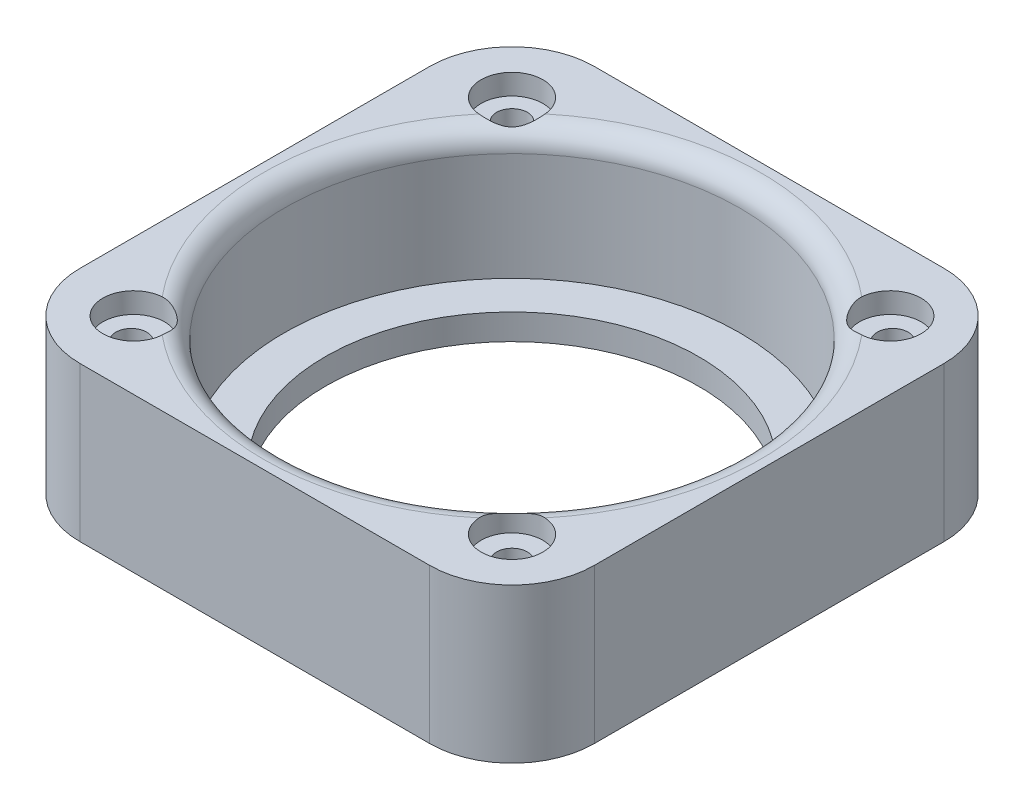
SolidWorks part; units mm, degrees
ref_plane "前视基准面" through (0, 0, 0) normal (0, 0, 1) x (1, 0, 0)
ref_plane "上视基准面" through (0, 0, 0) normal (0, 1, 0) x (1, 0, 0)
ref_plane "右视基准面" through (0, 0, 0) normal (1, 0, 0) x (0, 0, -1)
sketch "草图1" plane through (0, 0, 0) normal (0, 1, 0) x (1, 0, 0)
  circle A0 centre (0, 0) radius 25
extrude "凸台-拉伸1" add sketch "草图1" along normal blind 15
sketch "草图2" plane through (0, 15, 0) normal (0, 1, 0) x (1, 0, 0)
  circle A0 centre (0, 0) radius 22.15
  dimension "D1" = 44.3
extrude "切除-拉伸1" cut sketch "草图2" against normal blind 12.5
sketch "草图3" plane through (0, 2.5, 0) normal (0, 1, 0) x (1, 0, 0)
  circle A0 centre (0, 0) radius 18.15
  circle A1 centre (0, 0) radius 22.15 construction
  dimension "D1" = 4
extrude "切除-拉伸2" cut sketch "草图3" against normal blind 12.5
sketch "草图4" plane through (0, 0, 0) normal (0, 1, 0) x (1, 0, 0)
  line L1 (-25, 25) -> (25, 25)
  line L2 (-25, 25) -> (-25, -25)
  line L3 (-25, -25) -> (25, -25)
  line L4 (25, 25) -> (25, -25)
  line L5 (-25, 25) -> (25, -25) construction
  line L6 (-25, -25) -> (25, 25) construction
  circle A0 centre (0, 0) radius 25
  circle A1 centre (-18.3848, 18.3848) radius 1.5
  circle A2 centre (18.6152, 18.3848) radius 1.5
  circle A3 centre (18.6152, -18.6152) radius 1.5
  circle A4 centre (-18.3848, -18.6152) radius 1.5
  point P0 (0, 0)
  point P20 (0.1152, -0.1152)
  dimension "D3" = 3
  dimension "D4" = 26
  dimension "D6" = 37
  dimension "D7" = 37
  dimension "D1" = 50
  dimension "D2" = 50
  dimension "D5" = 4
extrude "凸台-拉伸2" add sketch "草图4" along normal blind 15 contours A0 L1 L2 | A0 L4 L1 | A0 L2 L3 | A0 L3 L4 region at (-19.4617, 0, -19.4617) region at (12.5, 0, -24.6464) region at (-23.5702, 0, 9.3406) region at (24.6464, 0, 12.5)
fillet "圆角1" radius 8 4 edges at (-25, 7.5, 25) (25, 7.5, 25) (25, 7.5, -25) (-25, 7.5, -25)
sketch "草图5" plane through (0, 15, 0) normal (0, 1, 0) x (1, 0, 0)
  circle A0 centre (-18.3848, 18.3848) radius 1.5
  circle A1 centre (18.6152, 18.3848) radius 1.5
  circle A2 centre (18.6152, -18.6152) radius 1.5
  circle A3 centre (-18.3848, -18.6152) radius 1.5
  point P12 (0.1152, -0.1152)
  dimension "D1" = 4
extrude "切除-拉伸3" cut sketch "草图5" against normal blind 15
sketch "草图6" plane through (0, 15, 0) normal (0, 1, 0) x (1, 0, 0)
  circle A0 centre (-18.3848, 18.3848) radius 3
  dimension "D1" = 6
extrude "切除-拉伸4" cut sketch "草图6" against normal blind 2
pattern_circular "阵列(圆周)1" count 4 over 360 about axis through (0, -10, 0) along (0, 1, 0) of "切除-拉伸4"
sketch "草图7" plane through (0, 0, 0) normal (0, -1, 0) x (1, 0, 0)
  line L0 (15.5416, 17.8176) -> (17.7692, 15.5546)
  line L1 (-15.3241, 17.7692) -> (-16.1217, 20.8428)
  line L2 (-16.1217, 20.8428) -> (-19.1824, 21.6888)
  line L3 (-19.1824, 21.6888) -> (-21.4454, 19.4613)
  line L4 (-21.4454, 19.4613) -> (-20.6478, 16.3877)
  line L5 (-20.6478, 16.3877) -> (-17.5872, 15.5416)
  line L6 (-17.5872, 15.5416) -> (-15.3241, 17.7692)
  line L7 (16.3877, 20.8783) -> (15.5416, 17.8176)
  line L8 (19.4613, 21.6759) -> (16.3877, 20.8783)
  line L9 (21.6888, 19.4128) -> (19.4613, 21.6759)
  line L10 (20.8428, 16.3522) -> (21.6888, 19.4128)
  line L11 (17.7692, 15.5546) -> (20.8428, 16.3522)
  line L12 (17.8176, -15.3112) -> (15.5546, -17.5387)
  line L13 (20.8783, -16.1572) -> (17.8176, -15.3112)
  line L14 (21.6759, -19.2308) -> (20.8783, -16.1572)
  line L15 (19.4128, -21.4584) -> (21.6759, -19.2308)
  line L16 (16.3522, -20.6123) -> (19.4128, -21.4584)
  line L17 (15.5546, -17.5387) -> (16.3522, -20.6123)
  line L18 (-15.3112, -17.5872) -> (-17.5387, -15.3241)
  line L19 (-16.1572, -20.6478) -> (-15.3112, -17.5872)
  line L20 (-19.2308, -21.4454) -> (-16.1572, -20.6478)
  line L21 (-21.4584, -19.1824) -> (-19.2308, -21.4454)
  line L22 (-20.6123, -16.1217) -> (-21.4584, -19.1824)
  line L23 (-17.5387, -15.3241) -> (-20.6123, -16.1217)
  circle A0 centre (-18.3848, 18.6152) radius 2.75 construction
  circle A1 centre (18.6152, 18.6152) radius 2.75 construction
  circle A2 centre (18.6152, -18.3848) radius 2.75 construction
  circle A3 centre (-18.3848, -18.3848) radius 2.75 construction
  point P36 (0.1152, 0.1152)
  dimension "D1" = 5.5
  dimension "D2" = 4
extrude "切除-拉伸5" cut sketch "草图7" against normal blind 10
sketch "草图9" plane through (0, 15, 0) normal (0, 1, 0) x (1, 0, 0)
  circle A0 centre (0, 0) radius 22.75 construction
  circle A1 centre (-22.75, 0) radius 1
  circle A2 centre (22.75, 0) radius 1
  dimension "D1" = 45.5
fillet "圆角2" radius 2 1 edges at (0, 15, 22.15)
